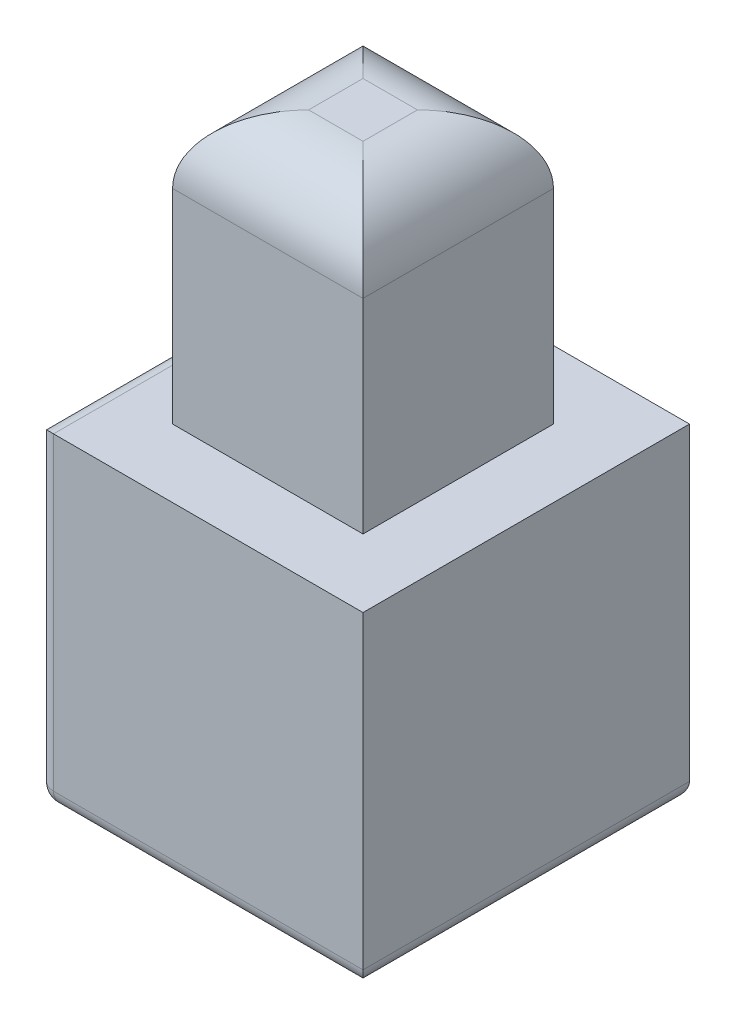
SolidWorks part; units mm, degrees
ref_plane "Front Plane" through (0, 0, 0) normal (0, 0, 1) x (1, 0, 0)
ref_plane "Top Plane" through (0, 0, 0) normal (0, 1, 0) x (1, 0, 0)
ref_plane "Right Plane" through (0, 0, 0) normal (1, 0, 0) x (0, 0, -1)
sketch "Sketch1" plane through (0, 0, 0) normal (0, 1, 0) x (1, 0, 0)
  line L1 (-2.4, 2.4) -> (2.4, 2.4)
  line L2 (-2.4, 2.4) -> (-2.4, -2.4)
  line L3 (-2.4, -2.4) -> (2.4, -2.4)
  line L4 (2.4, 2.4) -> (2.4, -2.4)
  line L5 (-2.4, 2.4) -> (2.4, -2.4) construction
  line L6 (-2.4, -2.4) -> (2.4, 2.4) construction
  point P0 (0, 0)
  dimension "D1" = 4.8
  dimension "D2" = 4.8
extrude "Boss-Extrude1" add sketch "Sketch1" along normal blind 4.8
sketch "Sketch2" plane through (0, 4.8, 0) normal (0, 1, 0) x (1, 0, 0)
  line L1 (-1.4, 1.4) -> (1.4, 1.4)
  line L2 (-1.4, 1.4) -> (-1.4, -1.4)
  line L3 (-1.4, -1.4) -> (1.4, -1.4)
  line L4 (1.4, 1.4) -> (1.4, -1.4)
  line L5 (-1.4, 1.4) -> (1.4, -1.4) construction
  line L6 (-1.4, -1.4) -> (1.4, 1.4) construction
  point P0 (0, 0)
  dimension "D1" = 2.8
  dimension "D2" = 2.8
extrude "Boss-Extrude2" add sketch "Sketch2" along normal blind 4
fillet "Fillet1" radius 1 4 edges at (0, 8.8, 1.4) (-1.4, 8.8, 0) (0, 8.8, -1.4) (1.4, 8.8, 0)
fillet "Fillet2" radius 0.25 4 edges at (0, 0, -2.4) (-2.4, 0, 0) (0, 0, 2.4) (2.4, 0, 0)
fillet "Fillet3" radius 0.25 5 edges at (-2.3268, 0.0732, 2.3268) (-2.3268, 0.0732, -2.3268) (-2.4, 4.8, 0) (-2.4, 2.525, 2.4) (-2.4, 2.525, -2.4)
